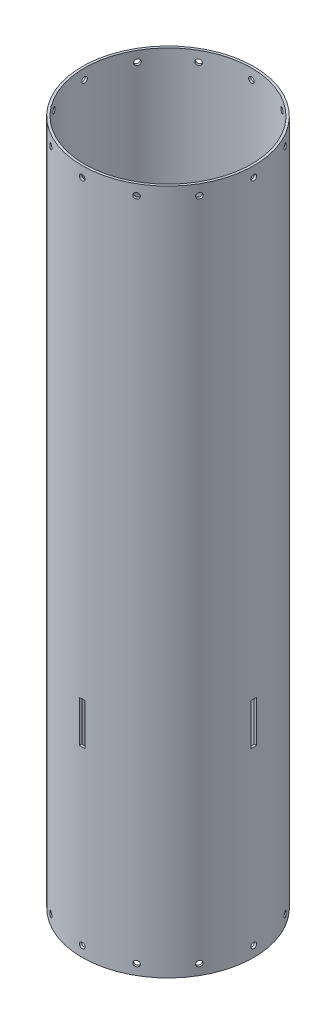
SolidWorks part; units mm, degrees
material "Fiberglass"
ref_plane "Front Plane" through (0, 0, 0) normal (0, 0, 1) x (1, 0, 0)
ref_plane "Top Plane" through (0, 0, 0) normal (0, 1, 0) x (1, 0, 0)
ref_plane "Right Plane" through (0, 0, 0) normal (1, 0, 0) x (0, 0, -1)
sketch "Sketch1" plane through (0, 0, 0) normal (0, 1, 0) x (1, 0, 0)
  circle A0 centre (0, 0) radius 76.2
  circle A1 centre (0, 0) radius 78.359
  dimension "D1" = 152.4
  dimension "D2" = 156.718
extrude "Boss-Extrude1" add sketch "Sketch1" along normal blind 626.11
sketch "Sketch2" plane through (0, 0, 0) normal (0, 0, 1) x (1, 0, 0)
  line L0 (0, 0) -> (0, 105.6712) construction
  line L1 (-76.2, 0) -> (76.2, 0) construction
  line L2 (-78.359, 0) -> (78.359, 0) construction
  line L3 (78.359, 313.055) -> (42.8908, 313.055) construction
  line L4 (78.359, 0) -> (78.359, 626.11) construction
  circle A0 centre (0, 9.525) radius 2.54
  circle A1 centre (0, 616.585) radius 2.54
  dimension "D1" = 5.08
  dimension "D2" = 9.525
extrude "Cut-Extrude1" cut sketch "Sketch2" against normal through all
ref_axis "Axis1" through (0, 0, 0) along (0, 1, 0)
pattern_circular "CirPattern1" count 12 over 360 about axis through (0, 0, 0) along (0, 1, 0) of "Cut-Extrude1" reverse direction yes
sketch "Sketch3" plane through (0, 0, 0) normal (0, 0, 1) x (1, 0, 0)
  line L0 (0, 0) -> (0, 105.6712) construction
  line L1 (-2.54, 166.37) -> (2.54, 166.37)
  line L2 (-2.54, 166.37) -> (-2.54, 204.47)
  line L3 (-2.54, 204.47) -> (2.54, 204.47)
  line L4 (2.54, 166.37) -> (2.54, 204.47)
  line L5 (-2.54, 166.37) -> (2.54, 204.47) construction
  line L6 (-2.54, 204.47) -> (2.54, 166.37) construction
  line L7 (-76.2, 0) -> (76.2, 0) construction
  line L8 (0, 626.11) -> (0, 408.1695) construction
  line L9 (76.2, 626.11) -> (-76.2, 626.11) construction
  point P0 (0, 185.42)
  dimension "D1" = 166.37
  dimension "D2" = 38.1
  dimension "D3" = 5.08
extrude "Cut-Extrude2" cut sketch "Sketch3" against normal through all
ref_axis "Axis2" through (0, 626.11, 0) along (0, -1, 0)
pattern_circular "CirPattern2" count 4 over 360 about axis through (0, 626.11, 0) along (0, -1, 0) of "Cut-Extrude2"
